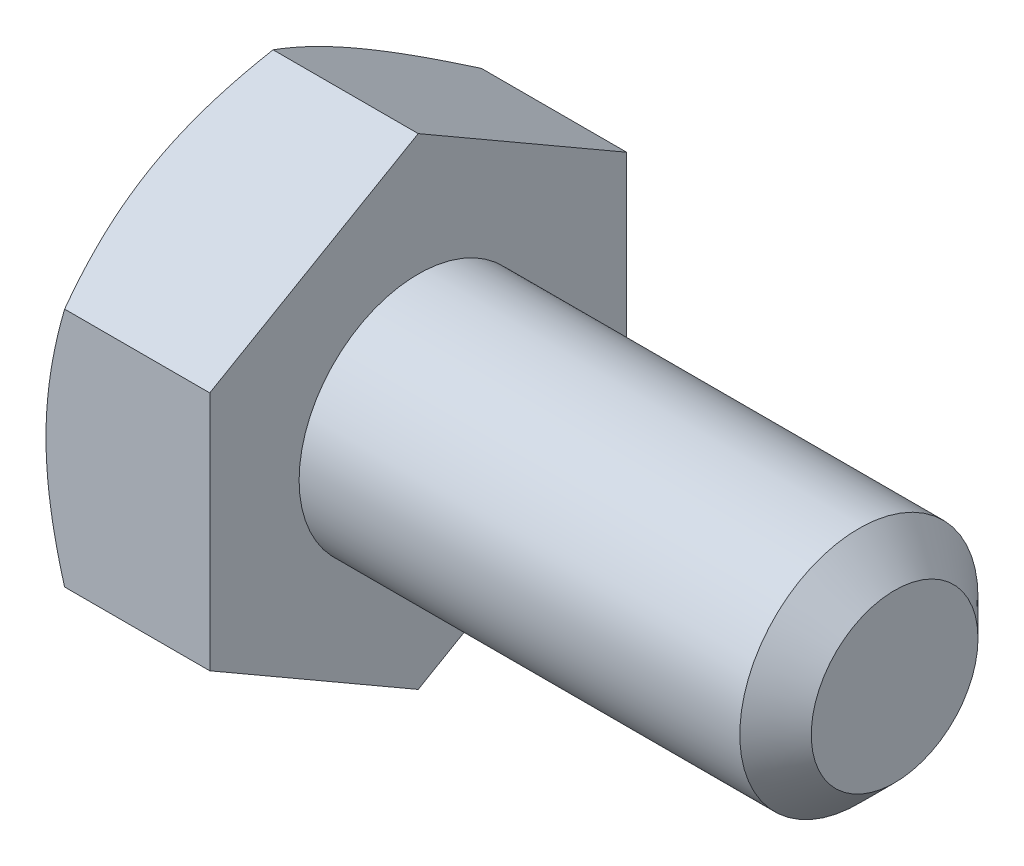
SolidWorks part; units mm, degrees
ref_plane "Front Plane" through (0, 0, 0) normal (0, 0, 1) x (1, 0, 0)
ref_plane "Top Plane" through (0, 0, 0) normal (0, 1, 0) x (1, 0, 0)
ref_plane "Right Plane" through (0, 0, 0) normal (1, 0, 0) x (0, 0, -1)
sketch "Sketch1" plane through (0, 0, 0) normal (0, 0, 1) x (1, 0, 0)
  line L0 (-8.5328, 0) -> (8.5328, 0) construction
  line L1 (8.5328, 3.175) -> (8.5328, -3.175) construction
  line L2 (-4.1672, 5.5562) -> (-4.1672, -5.5562) construction
  line L3 (-8.5328, 5.5562) -> (-8.5328, -5.5562) construction
  point P9 (-4.1672, 0)
  point P10 (4.0878, -3.175)
  dimension "Screw Dia" = 6.35
  dimension "Hex" = 11.1125
  dimension "Head Ht" = 4.3656
  dimension "Screw Lenght" = 12.7
  dimension "D1" = 4.445
ref_plane "Plane2" through (8.5328, 0, 0) normal (1, 0, 0) x (0, 0, -1)
sketch "Sketch5" plane through (8.5328, 0, 0) normal (1, 0, 0) x (0, 0, -1)
  circle A0 centre (0, 0) radius 3.175
extrude "Boss-Extrude3" add sketch "Sketch5" against normal up to vertex (12.7 mm away) up to point (-4.1672, 0, 0)
sketch "Sketch9" plane through (8.5328, 0, 0) normal (1, 0, 0) x (0, 0, -1)
  circle A1 centre (0, 0) radius 3.175
  circle A2 centre (0, 0) radius 3.175
  dimension "D1" = 0
curve "Helix/Spiral1" pitch 1.27 height 13.97 turns 11 parameters "Pitch"=1.27
chamfer "Chamfer1" distance 0.9525 angle 45 1 edges at (8.5328, 0, -3.175)
sketch "Sketch10" plane through (0, 0, 0) normal (0, 0, 1) x (1, 0, 0)
  line L0 (8.5328, 3.175) -> (9.0091, 2.3501)
  line L1 (9.0091, 2.3501) -> (9.1678, 2.3501)
  line L2 (9.1678, 2.3501) -> (9.6441, 3.175)
  line L3 (8.5328, 3.175) -> (9.6441, 3.175)
  line L4 (9.0884, 3.175) -> (9.0884, 2.3501) construction
  line L5 (8.7709, 2.7626) -> (9.4059, 2.7626) construction
  dimension "D1" = 60
  dimension "D2" = 0.1588
  dimension "D3" = 0.635
sweep "Cut-Sweep1" [suppressed] cut profiles "Sketch10" path "Helix/Spiral1"
sketch "Sketch11" plane through (0, 0, 0) normal (0, 0, 1) x (1, 0, 0)
  line L0 (-4.1672, 3.175) -> (-4.1672, 0)
  line L1 (-4.1672, 0) -> (-20.0422, 0)
  line L3 (-20.0422, 0) -> (-23.2172, 3.175)
  line L4 (-4.1672, 3.175) -> (-23.2172, 3.175)
  dimension "D1" = 45
  dimension "MIn Thread" = 31.75
revolve "Revolve1" [suppressed] add sketch "Sketch11" angle 360 about L1
sketch "Sketch6" plane through (-4.1672, 0, 0) normal (-1, 0, 0) x (0, 0, 1)
  line L0 (0, 5.5562) -> (0, -5.5562) construction
  line L1 (5.5562, 3.2079) -> (0, 6.4158)
  line L2 (0, 6.4158) -> (-5.5563, 3.2079)
  line L3 (-5.5563, 3.2079) -> (-5.5563, -3.2079)
  line L4 (-5.5563, -3.2079) -> (0, -6.4158)
  line L5 (0, -6.4158) -> (5.5563, -3.2079)
  line L6 (5.5563, -3.2079) -> (5.5562, 3.2079)
  circle A0 centre (0, 0) radius 5.5563 construction
extrude "Boss-Extrude4" add sketch "Sketch6" along normal up to vertex (4.3656 mm away) up to point (-8.5328, -5.5562, 0)
sketch "Sketch7" plane through (-8.5328, 0, 0) normal (-1, 0, 0) x (0, 0, 1)
  circle A0 centre (0, 0) radius 5.5563 construction
  circle A1 centre (0, 0) radius 5.5563
sketch "Sketch8" plane through (-8.5328, 0, 0) normal (-1, 0, 0) x (0, 0, 1)
  circle A0 centre (0, 0) radius 5.5563 construction
  circle A1 centre (0, 0) radius 5.5563
extrude "Cut-Extrude3" cut sketch "Sketch8" against normal through all draft 60 flip side to cut
equation "\"D2@Sketch10\" = \"Pitch@Helix/Spiral1\"*.125"
equation "\"D3@Sketch10\" = \"Pitch@Helix/Spiral1\"*.5"
equation "\"D3@Helix/Spiral1\" = \"Screw Lenght@Sketch1\"+\"Pitch@Helix/Spiral1\""
equation "\"D1@Chamfer1\" = \"Pitch@Helix/Spiral1\"*.75"
equation "\"D1@Sketch1\" = \"Pitch@Helix/Spiral1\"*3.5"
